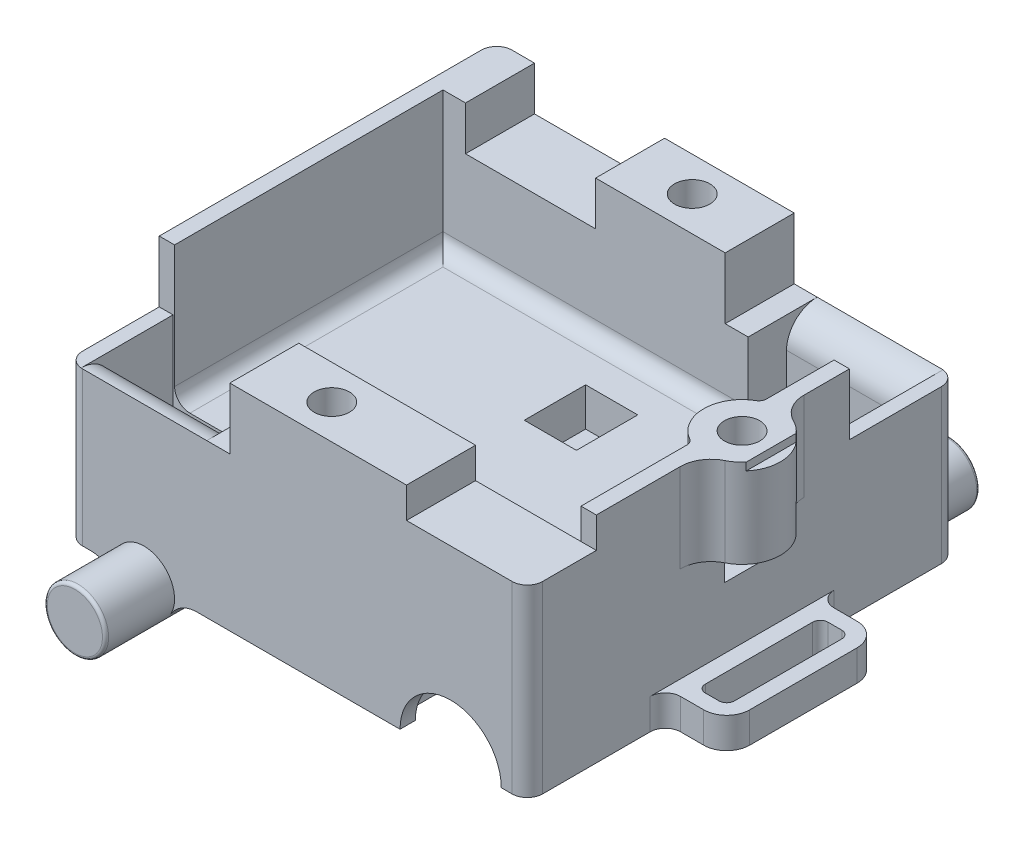
SolidWorks part; units mm, degrees
ref_plane "Front Plane" through (0, 0, 0) normal (0, 0, 1) x (1, 0, 0)
ref_plane "Top Plane" through (0, 0, 0) normal (0, 1, 0) x (1, 0, 0)
ref_plane "Right Plane" through (0, 0, 0) normal (1, 0, 0) x (0, 0, -1)
sketch "Sketch4" plane through (0, 0, 0) normal (0, 1, 0) x (1, 0, 0)
  line L1 (-14.8464, 7.0648) -> (15.1536, 7.0648)
  line L2 (-14.8464, 7.0648) -> (-14.8464, -20.9352)
  line L3 (-14.8464, -20.9352) -> (15.1536, -20.9352)
  line L4 (15.1536, 7.0648) -> (15.1536, -20.9352)
  dimension "D1" = 30
  dimension "D2" = 28
extrude "Boss-Extrude2" add sketch "Sketch4" along normal blind 14
sketch "Sketch20" plane through (0, 14, 0) normal (0, 1, 0) x (1, 0, 0)
  line L0 (-14.8464, -20.9352) -> (15.1536, -20.9352) construction
  line L1 (14.1536, -16.4352) -> (-13.8464, -16.4352)
  line L2 (14.1536, -16.4352) -> (14.1536, 2.5648)
  line L3 (14.1536, 2.5648) -> (-13.8464, 2.5648)
  line L4 (-13.8464, -16.4352) -> (-13.8464, 2.5648)
  line L5 (15.1536, -20.9352) -> (15.1536, 7.0648) construction
  dimension "D1" = 19
  dimension "D2" = 4.5
  dimension "D3" = 28
  dimension "D4" = 1
extrude "Cut-Extrude16" cut sketch "Sketch20" against normal blind 9
fillet "Fillet10" radius 1 4 edges at (0.1536, 5, 16.4352) (-13.8464, 5, 6.9352) (0.1536, 5, -2.5648) (14.1536, 5, 6.9352)
sketch "Sketch26" plane through (0, 0, 20.9352) normal (0, 0, 1) x (1, 0, 0)
  circle A0 centre (10.1536, 0) radius 4.1
  dimension "D1" = 8.2
extrude "Cut-Extrude17" cut sketch "Sketch26" against normal blind 26
sketch "Sketch27" plane through (0, 0, -7.0648) normal (0, 0, -1) x (-1, 0, 0)
  circle A0 centre (9.8464, 0) radius 4.1
  dimension "D1" = 8.2
extrude "Cut-Extrude18" cut sketch "Sketch27" against normal blind 26
sketch "Sketch28" plane through (0, 0, 0) normal (0, -1, 0) x (1, 0, 0)
  line L0 (-5.7464, 18.9352) -> (-5.7464, -7.0648) construction
  line L1 (-13.9464, -7.0648) -> (-5.7464, -7.0648)
  line L2 (-13.9464, -7.0648) -> (-13.9464, -6.0648)
  line L3 (-13.9464, -6.0648) -> (-5.7464, -6.0648)
  line L4 (-5.7464, -7.0648) -> (-5.7464, -6.0648)
  line L5 (14.2536, 20.9352) -> (14.2536, -5.0648) construction
  line L6 (6.0536, 20.9352) -> (14.2536, 20.9352)
  line L7 (6.0536, 20.9352) -> (6.0536, 19.9352)
  line L8 (6.0536, 19.9352) -> (14.2536, 19.9352)
  line L9 (14.2536, 20.9352) -> (14.2536, 19.9352)
  dimension "D1" = 1
  dimension "D2" = 1
extrude "Boss-Extrude6" add sketch "Sketch28" against normal blind 9
sketch "Sketch29" plane through (0, 0, -7.0648) normal (0, 0, -1) x (-1, 0, 0)
  circle A0 centre (9.8464, 0) radius 3.3
  dimension "D1" = 6.6
extrude "Cut-Extrude19" cut sketch "Sketch29" against normal blind 1
sketch "Sketch30" plane through (0, 0, 20.9352) normal (0, 0, 1) x (1, 0, 0)
  circle A0 centre (10.1536, 0) radius 3.3
  dimension "D1" = 6.6
extrude "Cut-Extrude20" cut sketch "Sketch30" against normal blind 1
sketch "Sketch31" plane through (0, 0, 18.9352) normal (0, 0, -1) x (-1, 0, 0)
  line L0 (5.7464, 0) -> (13.9464, 0) construction
  circle A0 centre (9.8464, 0) radius 2
  dimension "D1" = 4
extrude "Boss-Extrude7" add sketch "Sketch31" against normal blind 6.5
sketch "Sketch32" plane through (0, 0, -5.0648) normal (0, 0, 1) x (1, 0, 0)
  line L0 (6.0536, 0) -> (14.2536, 0) construction
  circle A0 centre (10.1536, 0) radius 2
  dimension "D1" = 4
extrude "Boss-Extrude8" add sketch "Sketch32" against normal blind 6.5
fillet "Fillet12" radius 2 4 edges at (-7.8464, 0, 19.9352) (-11.8464, 0, 19.9352) (8.1536, 0, -6.0648) (12.1536, 0, -6.0648)
sketch "Sketch33" plane through (0, 0, 0) normal (0, -1, 0) x (1, 0, 0)
  line L0 (14.2536, 19.9352) -> (14.2536, -5.0648) construction
  line L1 (6.0536, -5.0648) -> (14.2536, -5.0648)
  line L2 (6.0536, -5.0648) -> (6.0536, -3.5648)
  line L3 (6.0536, -3.5648) -> (14.2536, -3.5648)
  line L4 (14.2536, -5.0648) -> (14.2536, -3.5648)
  line L5 (-13.9464, -6.0648) -> (-13.9464, 18.9352) construction
  line L6 (-5.7464, 18.9352) -> (-13.9464, 18.9352)
  line L7 (-5.7464, 18.9352) -> (-5.7464, 17.4352)
  line L8 (-5.7464, 17.4352) -> (-13.9464, 17.4352)
  line L9 (-13.9464, 18.9352) -> (-13.9464, 17.4352)
  dimension "D1" = 1.5
  dimension "D2" = 1.5
extrude "Cut-Extrude21" cut sketch "Sketch33" against normal through all
fillet "Fillet13" radius 0.2 2 edges at (12.1536, 0, -11.5648) (-11.8464, 0, 25.4352)
fillet "Fillet15" radius 1 4 edges at (15.1536, 7, 20.9352) (15.1536, 7, -7.0648) (-14.8464, 7, -7.0648) (-14.8464, 7, 20.9352)
sketch "Sketch34" plane through (0, 14, 0) normal (0, 1, 0) x (1, 0, 0)
  line L0 (15.1536, -19.9352) -> (15.1536, 6.0648) construction
  circle A0 centre (15.1536, -6.9352) radius 2.5
  dimension "D1" = 5
extrude "Boss-Extrude9" add sketch "Sketch34" against normal blind 10
fillet "Fillet16" radius 1.5 1 edges at (17.6536, 4, 6.9352)
fillet "Fillet17" radius 2 5 edges at (15.1536, 9.75, 9.4352) (15.1536, 9.75, 4.4352) (15.1536, 4.4393, 8.9958) (15.1536, 4.4393, 4.8745) (15.1536, 4, 6.9352)
fillet "Fillet18" radius 0.5 5 edges at (13.9723, 5.4258, 9.1384) (13.8531, 5.2853, 4.8001) (14.1536, 10, 9.2264) (14.1536, 10, 4.6439) (12.6536, 5, 6.9352)
sketch "Sketch35" plane through (0, 14, 0) normal (0, 1, 0) x (1, 0, 0)
  circle A0 centre (15.1536, -6.9352) radius 1.15
  dimension "D1" = 2.3
extrude "Cut-Extrude22" cut sketch "Sketch35" against normal blind 8
sketch "Sketch36" plane through (0, 14, 0) normal (0, 1, 0) x (1, 0, 0)
  line L0 (14.1536, 2.5648) -> (-13.8464, 2.5648) construction
  line L1 (-14.8464, 6.0648) -> (-14.8464, -19.9352) construction
  line L2 (-13.8464, -20.9352) -> (14.1536, -20.9352) construction
  circle A0 centre (0.1536, -18.6852) radius 1.15
  circle A1 centre (0.1536, 4.8148) radius 1.15
  dimension "D1" = 2.3
  dimension "D2" = 2.3
  dimension "D3" = 2.25
  dimension "D4" = 15
  dimension "D5" = 2.25
  dimension "D6" = 15
extrude "Cut-Extrude23" cut sketch "Sketch36" against normal through all
sketch "Sketch37" plane through (0, 0, -5.0648) normal (0, 0, 1) x (1, 0, 0)
  line L0 (14.2536, 14) -> (14.2536, 0) construction
  line L1 (6.0536, 14) -> (14.2536, 14)
  line L2 (6.0536, 14) -> (6.0536, 10)
  line L3 (6.0536, 10) -> (14.2536, 10)
  line L4 (14.2536, 14) -> (14.2536, 10)
  dimension "D1" = 4
extrude "Cut-Extrude24" cut sketch "Sketch37" against normal blind 2
fillet "Fillet19" radius 2 1 edges at (10.1536, 10, -5.0648)
sketch "Sketch38" plane through (0, 0, 18.9352) normal (0, 0, -1) x (-1, 0, 0)
  line L0 (13.9464, 14) -> (13.9464, 0) construction
  line L1 (5.7464, 14) -> (13.9464, 14)
  line L2 (5.7464, 14) -> (5.7464, 10)
  line L3 (5.7464, 10) -> (13.9464, 10)
  line L4 (13.9464, 14) -> (13.9464, 10)
  dimension "D1" = 4
extrude "Cut-Extrude25" cut sketch "Sketch38" against normal blind 2
fillet "Fillet20" radius 2 1 edges at (-9.8464, 10, 18.9352)
sketch "Sketch39" plane through (0, 0, 0) normal (0, -1, 0) x (1, 0, 0)
  line L0 (15.1536, 19.9352) -> (15.1536, -6.0648) construction
  line L1 (6.6895, -7.0648) -> (-6.5464, -7.0648) construction
  line L2 (-6.3823, 20.9352) -> (6.8536, 20.9352) construction
  circle A0 centre (0.1536, 2.4352) radius 0.9
  circle A2 centre (0.1536, 11.4352) radius 0.9
  dimension "D1" = 15
  dimension "D2" = 15
  dimension "D3" = 9.5
  dimension "D4" = 9.5
  dimension "D5" = 1.8
  dimension "D6" = 1.8
extrude "Cut-Extrude26" cut sketch "Sketch39" against normal through all and the other way through all
sketch "Sketch40" plane through (0, 5, 0) normal (0, 1, 0) x (1, 0, 0)
  line L1 (-1.5464, -0.4352) -> (1.8536, -0.4352)
  line L2 (-1.5464, -0.4352) -> (-1.5464, -4.4352)
  line L3 (-1.5464, -4.4352) -> (1.8536, -4.4352)
  line L4 (1.8536, -0.4352) -> (1.8536, -4.4352)
  line L5 (-1.5464, -9.4352) -> (1.8536, -9.4352)
  line L6 (-1.5464, -9.4352) -> (-1.5464, -13.4352)
  line L7 (-1.5464, -13.4352) -> (1.8536, -13.4352)
  line L8 (1.8536, -9.4352) -> (1.8536, -13.4352)
  circle A0 centre (0.1536, -2.4352) radius 0.9 construction
  circle A1 centre (0.1536, -11.4352) radius 0.9 construction
  dimension "D1" = 3.4
  dimension "D2" = 3.4
  dimension "D3" = 4
  dimension "D4" = 4
  dimension "D5" = 2
  dimension "D6" = 1.7
  dimension "D7" = 1.7
  dimension "D8" = 2
extrude "Cut-Extrude27" cut sketch "Sketch40" against normal blind 2.5
sketch "Sketch41" plane through (0, 0, -7.0648) normal (0, 0, -1) x (-1, 0, 0)
  line L0 (-6.0536, 14) -> (13.8464, 14) construction
  line L1 (3.8964, 14) -> (12.3775, 14)
  line L2 (3.8964, 14) -> (3.8964, 11.1303)
  line L3 (3.8964, 11.1303) -> (12.3775, 11.1303)
  line L4 (12.3775, 14) -> (12.3775, 11.1303)
extrude "Cut-Extrude28" cut sketch "Sketch41" against normal blind 10
sketch "Sketch42" plane through (0, 0, -7.0648) normal (0, 0, -1) x (-1, 0, 0)
  line L1 (-6.0536, 10) -> (-16.2647, 10)
  line L2 (-6.0536, 10) -> (-6.0536, 14)
  line L3 (-6.0536, 14) -> (-16.2647, 14)
  line L4 (-16.2647, 10) -> (-16.2647, 14)
extrude "Cut-Extrude29" cut sketch "Sketch42" against normal blind 7
sketch "Sketch43" plane through (0, 14, 0) normal (0, 1, 0) x (1, 0, 0)
  line L0 (15.1536, -19.9352) -> (15.1536, -10.9663) construction
  line L1 (15.1536, -16.4352) -> (7.2753, -16.4352)
  line L2 (15.1536, -16.4352) -> (15.1536, -20.9352)
  line L3 (15.1536, -20.9352) -> (7.2753, -20.9352)
  line L4 (7.2753, -16.4352) -> (7.2753, -20.9352)
  line L5 (-5.7464, -20.9352) -> (14.1536, -20.9352) construction
extrude "Cut-Extrude30" cut sketch "Sketch43" against normal blind 2
sketch "Sketch44" plane through (0, 14, 0) normal (0, 1, 0) x (1, 0, 0)
  line L1 (17.052, -8.7906) -> (17.8177, -8.7906)
  line L2 (17.052, -8.7906) -> (17.052, -5.0159)
  line L3 (17.052, -5.0159) -> (17.8177, -5.0159)
  line L4 (17.8177, -8.7906) -> (17.8177, -5.0159)
extrude "Cut-Extrude31" cut sketch "Sketch44" against normal blind 0.5
sketch "Sketch45" plane through (0, 0, 20.9352) normal (0, 0, 1) x (1, 0, 0)
  line L1 (-5.7464, 10) -> (-15.5344, 10)
  line L2 (-5.7464, 10) -> (-5.7464, 14)
  line L3 (-5.7464, 14) -> (-15.5344, 14)
  line L4 (-15.5344, 10) -> (-15.5344, 14)
extrude "Cut-Extrude32" cut sketch "Sketch45" against normal up to surface (3.5 mm away) up to face at (-9.8464, 8.025, 17.4352)
sketch "Sketch46" plane through (0, 0, 20.9352) normal (0, 0, 1) x (1, 0, 0)
  line L0 (-5.7464, 14) -> (7.2753, 14) construction
  line L1 (-5.7464, 10) -> (-4.2464, 10)
  line L2 (-5.7464, 10) -> (-5.7464, 14)
  line L3 (-5.7464, 14) -> (-4.2464, 14)
  line L4 (-4.2464, 10) -> (-4.2464, 14)
  dimension "D1" = 1.5
extrude "Cut-Extrude33" cut sketch "Sketch46" against normal up to surface (3.5 mm away) up to face at (-11.5131, 8.6833, 17.4352)
sketch "Sketch47" plane through (0, 0, 17.4352) normal (0, 0, 1) x (1, 0, 0)
  line L1 (-14.8464, 10) -> (-4.2464, 10)
  line L2 (-14.8464, 10) -> (-14.8464, 14)
  line L3 (-14.8464, 14) -> (-4.2464, 14)
  line L4 (-4.2464, 10) -> (-4.2464, 14)
extrude "Cut-Extrude34" cut sketch "Sketch47" against normal blind 2.5
sketch "Sketch48" plane through (0, 0, -7.0648) normal (0, 0, -1) x (-1, 0, 0)
  line L0 (-6.0536, 14) -> (3.8964, 14) construction
  line L1 (-6.0536, 10) -> (-4.5536, 10)
  line L2 (-6.0536, 10) -> (-6.0536, 14)
  line L3 (-6.0536, 14) -> (-4.5536, 14)
  line L4 (-4.5536, 10) -> (-4.5536, 14)
  dimension "D1" = 1.5
extrude "Cut-Extrude35" cut sketch "Sketch48" against normal blind 4.5
sketch "Sketch49" plane through (0, 0, 0) normal (0, -1, 0) x (1, 0, 0)
  circle A0 centre (-3.5474, -1.7648) radius 2
  circle A1 centre (-3.5474, 15.6352) radius 2
  circle A2 centre (3.8526, 15.6352) radius 2
  dimension "D1" = 4
  dimension "D2" = 4
  dimension "D3" = 4
extrude "Cut-Extrude36" cut sketch "Sketch49" against normal blind 1.5
sketch "Sketch50" plane through (0, 0, 0) normal (0, -1, 0) x (1, 0, 0)
  line L0 (-5.1274, -3.3648) -> (-5.1274, 17.2352) construction
  line L1 (-5.1274, 14.9352) -> (5.4346, 14.9352)
  line L2 (-5.1274, 14.9352) -> (-5.1274, -1.0648)
  line L3 (-5.1274, -1.0648) -> (5.4346, -1.0648)
  line L4 (5.4346, 14.9352) -> (5.4346, -1.0648)
  line L5 (5.4346, 17.2352) -> (5.4346, 6.4629) construction
  line L6 (6.6895, -7.0648) -> (-6.5464, -7.0648) construction
  line L7 (-6.3823, 20.9352) -> (6.8536, 20.9352) construction
  dimension "D1" = 6
  dimension "D2" = 6
extrude "Cut-Extrude37" cut sketch "Sketch50" against normal blind 1.5
sketch "Sketch51" plane through (0, 10, 0) normal (0, 1, 0) x (1, 0, 0)
  line L1 (-5.7464, -17.4352) -> (-13.8464, -17.4352)
  line L2 (-5.7464, -17.4352) -> (-5.7464, -14.9352)
  line L3 (-5.7464, -14.9352) -> (-13.8464, -14.9352)
  line L4 (-13.8464, -17.4352) -> (-13.8464, -14.9352)
  line L5 (6.0536, 3.5648) -> (14.1536, 3.5648)
  line L6 (6.0536, 3.5648) -> (6.0536, 0.0648)
  line L7 (6.0536, 0.0648) -> (14.1536, 0.0648)
  line L8 (14.1536, 3.5648) -> (14.1536, 0.0648)
extrude "Cut-Extrude38" cut sketch "Sketch51" against normal up to surface (5 mm away) up to face at (0.1536, 5, 2.4352)
sketch "Sketch52" plane through (0, 0, 18.9352) normal (0, 0, -1) x (-1, 0, 0)
  circle A0 centre (9.8464, 0) radius 1.5
extrude "Boss-Extrude10" add sketch "Sketch52" along normal blind 0.5
sketch "Sketch53" plane through (0, 0, -5.0648) normal (0, 0, 1) x (1, 0, 0)
  circle A0 centre (10.1536, 0) radius 1.5
extrude "Boss-Extrude11" add sketch "Sketch53" along normal blind 0.5
sketch "Sketch54" plane through (0, 5, 0) normal (0, 1, 0) x (1, 0, 0)
  line L0 (-14.8464, -14.9352) -> (-13.8464, -14.9352) construction
  line L1 (-5.7464, -17.4352) -> (-13.9464, -17.4352)
  line L2 (-5.7464, -17.4352) -> (-5.7464, -14.9352)
  line L3 (-5.7464, -14.9352) -> (-13.9464, -14.9352)
  line L4 (-13.9464, -17.4352) -> (-13.9464, -14.9352)
extrude "Cut-Extrude39" cut sketch "Sketch54" against normal through all both and the other way through all
sketch "Sketch56" plane through (0, 5, 0) normal (0, 1, 0) x (1, 0, 0)
  line L0 (15.1536, 0.0648) -> (14.1536, 0.0648) construction
  line L1 (6.0536, 3.5648) -> (14.2536, 3.5648)
  line L2 (6.0536, 3.5648) -> (6.0536, 0.0648)
  line L3 (6.0536, 0.0648) -> (14.2536, 0.0648)
  line L4 (14.2536, 3.5648) -> (14.2536, 0.0648)
extrude "Cut-Extrude41" cut sketch "Sketch56" against normal through all both and the other way through all
sketch "Sketch58" plane through (0, 0, 18.9352) normal (0, 0, -1) x (-1, 0, 0)
  circle A0 centre (9.8464, 0) radius 1.75
  dimension "D1" = 3.5
extrude "Boss-Extrude12" add sketch "Sketch58" along normal blind 0.8
sketch "Sketch59" plane through (0, 0, -5.0648) normal (0, 0, 1) x (1, 0, 0)
  circle A0 centre (10.1536, 0) radius 1.75
  dimension "D1" = 3.5
extrude "Boss-Extrude13" add sketch "Sketch59" along normal blind 0.8
fillet "Fillet21" radius 0.5 1 edges at (-11.5964, 0, 18.1352)
fillet "Fillet22" radius 0.5 1 edges at (11.9036, 0, -4.2648)
sketch "Sketch60" plane through (15.1536, 0, 0) normal (1, 0, 0) x (0, 0, -1)
  line L0 (-19.9352, 0) -> (6.0648, 0) construction
  line L1 (-11.9352, 0) -> (-1.9352, 0)
  line L2 (-11.9352, 0) -> (-11.9352, 2)
  line L3 (-11.9352, 2) -> (-1.9352, 2)
  line L4 (-1.9352, 0) -> (-1.9352, 2)
  line L5 (-20.9352, 0) -> (-20.9352, 12) construction
  line L6 (7.0648, 10) -> (7.0648, 0) construction
  dimension "D1" = 9
  dimension "D2" = 9
  dimension "D3" = 2
extrude "Boss-Extrude14" add sketch "Sketch60" along normal blind 4
fillet "Fillet23" radius 1 2 edges at (15.1536, 1, 1.9352) (15.1536, 1, 11.9352)
sketch "Sketch61" plane through (0, 0, 0) normal (0, -1, 0) x (1, 0, 0)
  line L0 (19.1536, 11.9352) -> (19.1536, 1.9352) construction
  line L1 (18.1536, 10.9352) -> (16.2536, 10.9352)
  line L2 (18.1536, 10.9352) -> (18.1536, 2.9352)
  line L3 (18.1536, 2.9352) -> (16.2536, 2.9352)
  line L4 (16.2536, 10.9352) -> (16.2536, 2.9352)
  line L5 (14.2536, -5.0648) -> (14.2536, -0.0648) construction
  line L6 (19.1536, 1.9352) -> (16.1536, 1.9352) construction
  line L7 (19.1536, 11.9352) -> (16.1536, 11.9352) construction
  dimension "D1" = 1
  dimension "D2" = 2
  dimension "D3" = 1
  dimension "D4" = 1
extrude "Cut-Extrude42" cut sketch "Sketch61" against normal blind 2
fillet "Fillet25" radius 1.5 2 edges at (19.1536, 1, 11.9352) (19.1536, 1, 1.9352)
fillet "Fillet26" radius 0.5 4 edges at (18.1536, 1, 2.9352) (18.1536, 1, 10.9352) (16.2536, 1, 10.9352) (16.2536, 1, 2.9352)
sketch "Sketch62" plane through (15.1536, 0, 0) normal (1, 0, 0) x (0, 0, -1)
  line L1 (-12.4652, 8.2228) -> (-1.7303, 8.2228)
  line L2 (-12.4652, 8.2228) -> (-12.4652, 2.1044)
  line L3 (-12.4652, 2.1044) -> (-1.7303, 2.1044)
  line L4 (-1.7303, 8.2228) -> (-1.7303, 2.1044)
extrude "Cut-Extrude43" cut sketch "Sketch62" along normal blind 4
